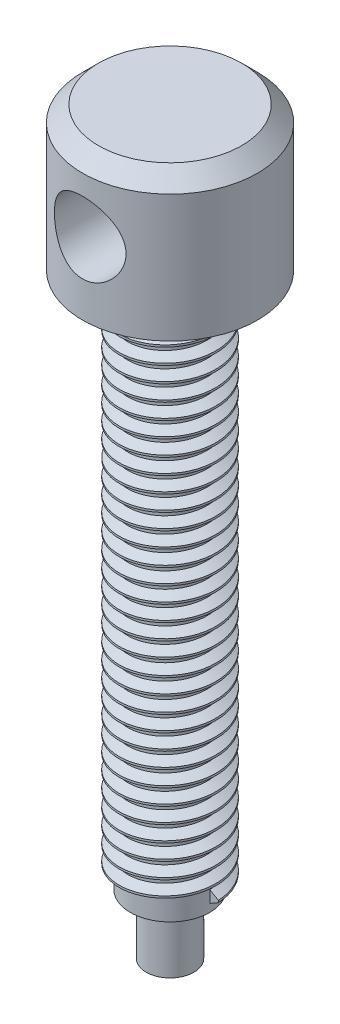
SolidWorks part; units mm, degrees
ref_plane "Front Plane" through (0, 0, 0) normal (0, 0, 1) x (1, 0, 0)
ref_plane "Top Plane" through (0, 0, 0) normal (0, 1, 0) x (1, 0, 0)
ref_plane "Right Plane" through (0, 0, 0) normal (1, 0, 0) x (0, 0, -1)
sketch "Sketch1" plane through (0, 0, 0) normal (0, 0, 1) x (1, 0, 0)
  line L0 (0, 0) -> (0, 109.5147) construction
  line L1 (0, 0) -> (0, 93)
  line L2 (0, 93) -> (9, 93)
  line L3 (11, 91) -> (11, 75)
  line L4 (11, 75) -> (5, 75)
  line L5 (5, 75) -> (5, 7.5149)
  line L6 (3, 0) -> (0, 0)
  line L7 (0, 93) -> (11, 93)
  line L8 (0, 0) -> (0, -8.7332) construction
  line L9 (3, 8) -> (3, 0)
  line L10 (9, 93) -> (11, 91)
  arc A0 (5, 7.5149) -> (3, 8) centre (0, -8.7332) ccw
  point P12 (3.8024, 0)
  dimension "D6" = 17
  dimension "D7" = 8
  dimension "D1" = 93
  dimension "D2" = 18
  dimension "D3" = 22
  dimension "D4" = 10
  dimension "D5" = 6
revolve "Revolve1" add sketch "Sketch1" angle 360 about L0
sketch "Sketch2" plane through (0, 0, 0) normal (0, 0, 1) x (1, 0, 0)
  line L0 (0, 0) -> (0, 93) construction
  line L1 (9, 93) -> (-9, 93) construction
  circle A0 centre (0, 84) radius 4.5
  dimension "D1" = 9
  dimension "D2" = 9
extrude "Cut-Extrude1" cut sketch "Sketch2" against normal through all both and the other way through all
thread "Thread1" pitch 2 profile "Thread Profile1" start angle 0, offset 2, length 65, pitch 2, diameter 10
ref_plane "Plane1" through (-5, 73, 0) normal (0, 0, 1) x (-1, 0, 0)
sketch "Thread Profile1" plane through (-5, 73, 0) normal (0, 0, 1) x (-1, 0, 0)
  line L0 (0, 0) -> (0, 2) construction
  line L1 (0, 0) -> (1.0825, 0.625)
  line L2 (1.0825, 0.625) -> (1.0825, 0.875)
  line L3 (1.0825, 0.875) -> (0, 1.5)
  line L4 (1.0825, 0.75) -> (0, 0.75) construction
  line L11 (0, 0) -> (0, 1.5)
  point P2 (0, 0)
  dimension "Pitch" = 2
  dimension "Profile_Angle" = 60
  dimension "Profile_Land" = 0.25
  dimension "Profile_Height" = 1.0825
